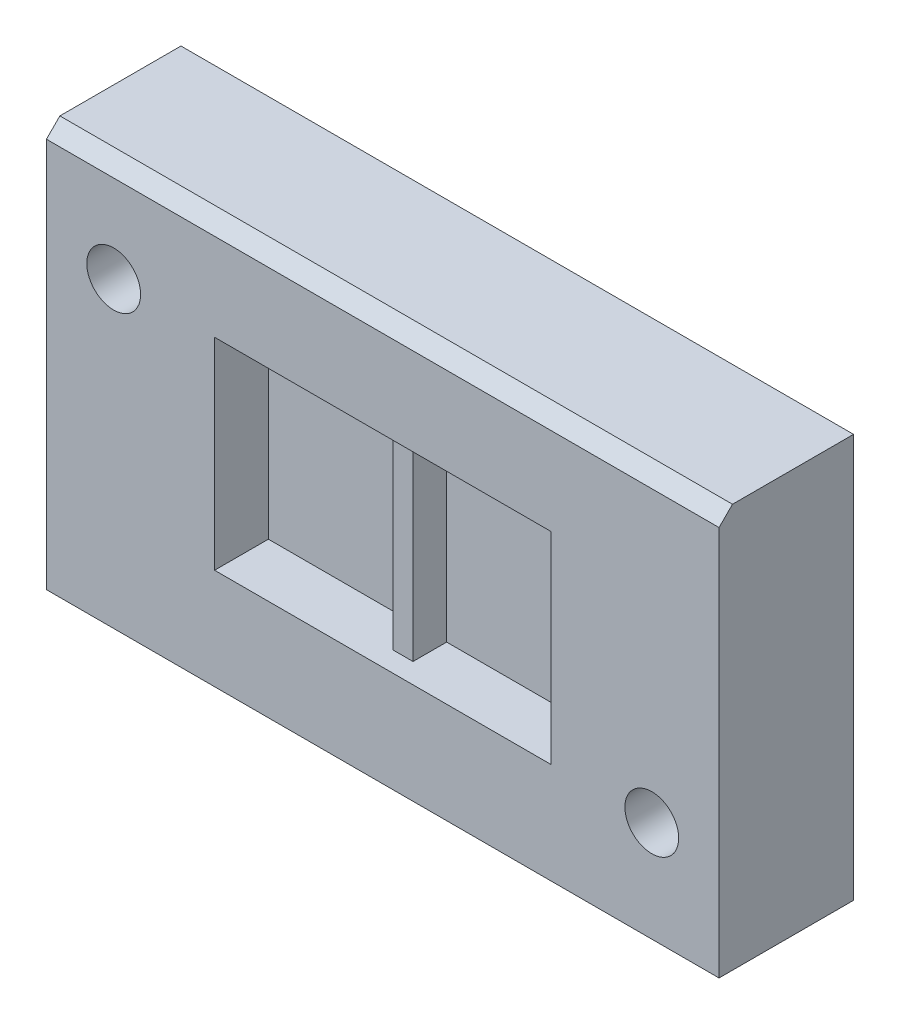
SolidWorks part; units mm, degrees
material "1.0038 (S235JRG2)"
ref_plane "Ebene vorne" through (0, 0, 0) normal (0, 0, 1) x (1, 0, 0)
ref_plane "Ebene oben" through (0, 0, 0) normal (0, 1, 0) x (1, 0, 0)
ref_plane "Ebene rechts" through (0, 0, 0) normal (1, 0, 0) x (0, 0, -1)
sketch "Skizze1" plane through (0, 0, 0) normal (0, 0, 1) x (1, 0, 0)
  line L1 (-50, -30) -> (50, -30)
  line L2 (-50, -30) -> (-50, 30)
  line L3 (-50, 30) -> (50, 30)
  line L4 (50, -30) -> (50, 30)
  dimension "D1" = 100
  dimension "D2" = 60
  dimension "D3" = 50
  dimension "D4" = 30
extrude "Aufsatz-Linear austragen1" add sketch "Skizze1" along normal blind 20
sketch "Skizze2" plane through (0, 0, 20) normal (0, 0, 1) x (1, 0, 0)
  line L1 (-25, -15) -> (25, -15)
  line L2 (-25, -15) -> (-25, 15)
  line L3 (-25, 15) -> (25, 15)
  line L4 (25, -15) -> (25, 15)
  dimension "D1" = 50
  dimension "D2" = 30
  dimension "D3" = 25
  dimension "D4" = 15
  dimension "D5" = 50
extrude "Schnitt-Linear austragen1" cut sketch "Skizze2" against normal blind 8
sketch "Skizze3" plane through (0, 0, 20) normal (0, 0, 1) x (1, 0, 0)
  circle A0 centre (-40, 15) radius 4
  dimension "D2" = 40
  dimension "D3" = 15
  dimension "Bohrung_D" = 8
extrude "Schnitt-Linear austragen2" cut sketch "Skizze3" against normal through all
sketch "Skizze4" plane through (0, 0, 20) normal (0, 0, 1) x (1, 0, 0)
  circle A0 centre (40, -15) radius 4
  dimension "D2" = 40
  dimension "D3" = 15
  dimension "Bohrung_D" = 8
extrude "Schnitt-Linear austragen3" cut sketch "Skizze4" against normal through all
sketch "Skizze5" plane through (0, 0, 0) normal (1, 0, 0) x (0, 0, -1)
  line L0 (-17, -10) -> (-17, 10)
rib "Verstärkungsrippe1" sketch "Skizze5" sketch "Skizze5" thickness 3 extrusion direction parallel to sketch draft on no parameters "D1"=3
chamfer "Fase1" distance 2 angle 45 1 edges at (0, 30, 20)
equation "\"L\" = 100"
equation "\"D1@Skizze1\" = \"L\""
